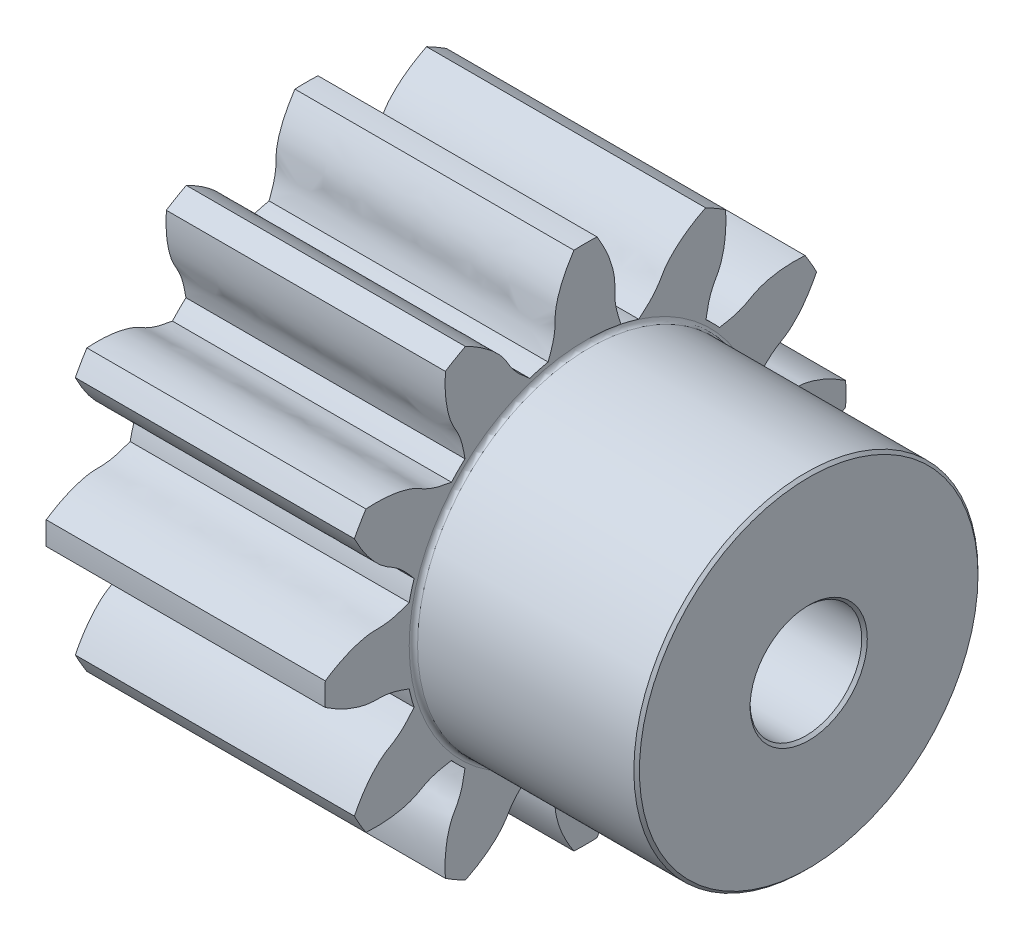
SolidWorks part; units mm, degrees
ref_plane "Front Plane" through (0, 0, 0) normal (0, 0, 1) x (1, 0, 0)
ref_plane "Top Plane" through (0, 0, 0) normal (0, 1, 0) x (1, 0, 0)
ref_plane "Right Plane" through (0, 0, 0) normal (1, 0, 0) x (0, 0, -1)
ref_plane "Plane1" through (7.5, 0, 0) normal (1, 0, 0) x (0, 0, -1)
sketch "Sketch1" plane through (7.5, 0, 0) normal (1, 0, 0) x (0, 0, -1)
  arc A0 (12.4228, 6.4556) -> (-0.6207, 13.9862) centre (0, 0) ccw
  arc A1 (-2.008, 9.4756) -> (9.2101, 2.9988) centre (0, 0) ccw
  spline S0 degree 3 poles (9.2101, 2.9988) (9.3028, 3.1083) (9.3947, 3.2185) (9.4883, 3.3272) (9.7708, 3.6554) (10.1044, 3.9535) (10.4843, 4.1613) (10.8434, 4.3576) (11.1602, 4.6361) (11.4312, 4.9428) (11.6966, 5.2432) (11.9287, 5.5745) (12.1331, 5.9193) (12.2366, 6.0941) (12.3331, 6.2733) (12.4228, 6.4556) knots -0.000425 -0.000425 -0.000425 -0.000425 0 0 0 0.001299 0.001299 0.001299 0.002525 0.002525 0.002525 0.003717 0.003717 0.003717 0.00432 0.00432 0.00432 0.00432
  spline S1 degree 3 poles (-0.6207, 13.9862) (-0.7337, 13.8174) (-0.8406, 13.6443) (-0.9402, 13.4672) (-1.2112, 12.9854) (-1.4376, 12.4679) (-1.559, 11.9286) (-1.6197, 11.6591) (-1.6428, 11.3796) (-1.6371, 11.1034) (-1.63, 10.7529) (-1.6999, 10.4) (-1.8024, 10.0647) (-1.8212, 10.0029) (-1.8414, 9.9416) (-1.8627, 9.8807) (-1.9101, 9.7452) (-1.9595, 9.6106) (-2.008, 9.4756) knots -0.000605 -0.000605 -0.000605 -0.000605 0 0 0 0.001658 0.001658 0.001658 0.002483 0.002483 0.002483 0.00354 0.00354 0.00354 0.003732 0.003732 0.003732 0.004161 0.004161 0.004161 0.004161
extrude "Boss-Extrude1" add sketch "Sketch1" against normal blind 15
sketch "Sketch2" plane through (-7.5, 0, 0) normal (-1, 0, 0) x (0, 0, 1)
  arc A0 (-7.5307, 11.8021) -> (-11.8021, 7.5307) centre (0, 0) ccw
  arc A1 (-7.2021, 6.4768) -> (-6.4768, 7.2021) centre (0, 0) cw
  spline S0 degree 3 poles (-11.8021, 7.5307) (-11.5994, 7.5441) (-11.396, 7.5502) (-11.1928, 7.5479) (-10.6401, 7.5416) (-10.0787, 7.479) (-9.551, 7.3145) (-9.2872, 7.2323) (-9.0337, 7.1125) (-8.7973, 6.9695) (-8.4973, 6.788) (-8.1567, 6.6721) (-7.8151, 6.5932) (-7.7522, 6.5787) (-7.689, 6.5655) (-7.6255, 6.5535) (-7.4846, 6.5268) (-7.3432, 6.5023) (-7.2021, 6.4768) knots -0.000605 -0.000605 -0.000605 -0.000605 0 0 0 0.001658 0.001658 0.001658 0.002483 0.002483 0.002483 0.00354 0.00354 0.00354 0.003732 0.003732 0.003732 0.004161 0.004161 0.004161 0.004161
  spline S1 degree 3 poles (-6.4768, 7.2021) (-6.5023, 7.3432) (-6.5268, 7.4846) (-6.5535, 7.6255) (-6.6341, 8.051) (-6.7739, 8.476) (-6.999, 8.8459) (-7.2118, 9.1955) (-7.347, 9.5951) (-7.4283, 9.9962) (-7.508, 10.3891) (-7.5434, 10.792) (-7.5479, 11.1928) (-7.5502, 11.396) (-7.5441, 11.5994) (-7.5307, 11.8021) knots -0.000425 -0.000425 -0.000425 -0.000425 0 0 0 0.001299 0.001299 0.001299 0.002525 0.002525 0.002525 0.003717 0.003717 0.003717 0.00432 0.00432 0.00432 0.00432
extrude "Cut-Extrude1" cut sketch "Sketch2" against normal through all
sketch "Sketch3" plane through (-7.5, 0, 0) normal (-1, 0, 0) x (0, 0, 1)
  arc A0 (-0.6207, 13.9862) -> (-6.4556, 12.4228) centre (0, 0) ccw
  arc A1 (-2.9988, 9.2101) -> (-2.008, 9.4756) centre (0, 0) cw
  spline S0 degree 3 poles (-6.4556, 12.4228) (-6.2733, 12.3331) (-6.0941, 12.2366) (-5.9193, 12.1331) (-5.4438, 11.8513) (-4.9889, 11.5163) (-4.6141, 11.11) (-4.4268, 10.9069) (-4.2671, 10.6764) (-4.1339, 10.4344) (-3.9648, 10.1272) (-3.7278, 9.8566) (-3.4714, 9.6174) (-3.4242, 9.5734) (-3.3761, 9.5304) (-3.3272, 9.4883) (-3.2185, 9.3947) (-3.1083, 9.3028) (-2.9988, 9.2101) knots -0.000605 -0.000605 -0.000605 -0.000605 0 0 0 0.001658 0.001658 0.001658 0.002483 0.002483 0.002483 0.00354 0.00354 0.00354 0.003732 0.003732 0.003732 0.004161 0.004161 0.004161 0.004161
  spline S1 degree 3 poles (-2.008, 9.4756) (-1.9595, 9.6106) (-1.9101, 9.7452) (-1.8627, 9.8807) (-1.7198, 10.2894) (-1.6284, 10.7274) (-1.6384, 11.1603) (-1.6479, 11.5695) (-1.5651, 11.9831) (-1.435, 12.3711) (-1.3076, 12.7512) (-1.1367, 13.1178) (-0.9402, 13.4672) (-0.8406, 13.6443) (-0.7337, 13.8174) (-0.6207, 13.9862) knots -0.000425 -0.000425 -0.000425 -0.000425 0 0 0 0.001299 0.001299 0.001299 0.002525 0.002525 0.002525 0.003717 0.003717 0.003717 0.00432 0.00432 0.00432 0.00432
extrude "Cut-Extrude2" cut sketch "Sketch3" against normal through all
sketch "Sketch4" plane through (0, 0, 0) normal (0, 0, 1) x (1, 0, 0)
  line L0 (7.5, 9.25) -> (7.5, 0)
  line L1 (7.5, 0) -> (19.5, 0)
  line L2 (19.5, 0) -> (19.5, 9.25)
  line L3 (19.5, 9.25) -> (7.5, 9.25)
  line L4 (7.5, 0) -> (19.5, 0) construction
revolve "Revolve1" add sketch "Sketch4" angle 360 about L4 reverse direction yes
hole_wizard "Ø6.0 (6) Diameter Hole1" positions "Sketch6" profile "Sketch5" hole size "Ø6.0" standard "ANSI Metric"
sketch "Sketch6" plane through (-7.5, 0, 0) normal (-1, 0, 0) x (0, 0, 1)
  point P0 (0, 0)
sketch "Sketch5" plane through (-7.5, 0, 0) normal (0, 1, 0) x (0, 0, 1)
  line L0 (0, 0) -> (0, 27)
  line L1 (0, 27) -> (3, 27)
  line L2 (3, 27) -> (3, 0)
  line L5 (3, 0) -> (0, 0)
  line L11 (0, -6.35) -> (0, 107.95) construction
  dimension "Thru Hole Dia." = 6
  dimension "Thru Hole Depth" = 27
chamfer "Chamfer1" distance 0.15 angle 45 3 edges at (19.5, 0, -9.25) (19.5, 0, 3) (-7.5, 0, 3)
fillet "Fillet1" radius 0.225 1 edges at (7.5, 0, -9.25) tangent propagation no
fillet "Fillet2" radius 0.5 6 edges at (-7.5, 12.1244, -7) (-7.5, 7, -12.1244) (7.5, 14, 0) (-7.5, 14, 0) (7.5, 12.1244, -7) (7.5, 7, -12.1244) tangent propagation no
fillet "Fillet3" radius 0.78 6 edges at (0, 9.2101, -2.9988) (0, 2.9988, -9.2101) (0, 9.4756, 2.008) (0, 6.4768, -7.2021) (0, 7.2021, -6.4768) (0, 9.4756, -2.008) tangent propagation no
pattern_circular "CirPattern2" count 12 over 360 about axis through (7.5, 0, 0) along (1, 0, 0) of "Cut-Extrude2", "Boss-Extrude1"
sketch "Sketch7" plane through (7.5, 0, 0) normal (1, 0, 0) x (0, 0, -1)
  line L0 (-0.6207, 13.9862) -> (0.6207, 13.9862)
  line L1 (6.4556, 12.4228) -> (7.5307, 11.8021)
  arc A0 (6.4556, 12.4228) -> (0.6207, 13.9862) centre (0, 0) ccw
  arc A1 (1.9084, 9.2808) -> (2.8633, 9.032) centre (0, 0) cw
  arc A3 (7.5307, 11.8021) -> (-0.6207, 13.9862) centre (0, 0) ccw construction
  circle A4 centre (0, 0) radius 9.475 construction
  spline S0 degree 3 poles (0.6207, 13.9862) (0.732, 13.8081) (0.8369, 13.6258) (0.9341, 13.4396) (1.1985, 12.933) (1.4157, 12.391) (1.5237, 11.8299) (1.5777, 11.5494) (1.5925, 11.26) (1.5778, 10.9747) (1.5591, 10.6128) (1.6199, 10.2459) (1.7149, 9.8961) (1.7324, 9.8317) (1.7513, 9.7677) (1.7713, 9.7041) (1.8159, 9.5626) (1.8627, 9.4219) (1.9084, 9.2808) knots -0.000605 -0.000605 -0.000605 -0.000605 0 0 0 0.001658 0.001658 0.001658 0.002483 0.002483 0.002483 0.00354 0.00354 0.00354 0.003732 0.003732 0.003732 0.004161 0.004161 0.004161 0.004161
  spline S1 degree 3 poles (2.8633, 9.032) (2.9772, 9.1299) (3.0918, 9.227) (3.2048, 9.3258) (3.546, 9.6242) (3.8554, 9.9758) (4.0698, 10.3752) (4.2724, 10.7526) (4.5614, 11.0865) (4.8802, 11.3726) (5.1924, 11.6529) (5.5373, 11.8985) (5.8966, 12.1152) (6.0787, 12.225) (6.2655, 12.3274) (6.4556, 12.4228) knots -0.000425 -0.000425 -0.000425 -0.000425 0 0 0 0.001299 0.001299 0.001299 0.002525 0.002525 0.002525 0.003717 0.003717 0.003717 0.00432 0.00432 0.00432 0.00432
  circle M1 centre (0, 0) radius 9.475
  arc M4 (7.5307, 11.8021) -> (-0.6207, 13.9862) centre (0, 0) ccw
  dimension "D2" = 6.0407
  dimension "D1" = 0.9868
extrude "Cut-Extrude3" cut sketch "Sketch7" against normal through all contours S1 S0 M1 M4 region at (7.5, 11.8074, -3.1367)
